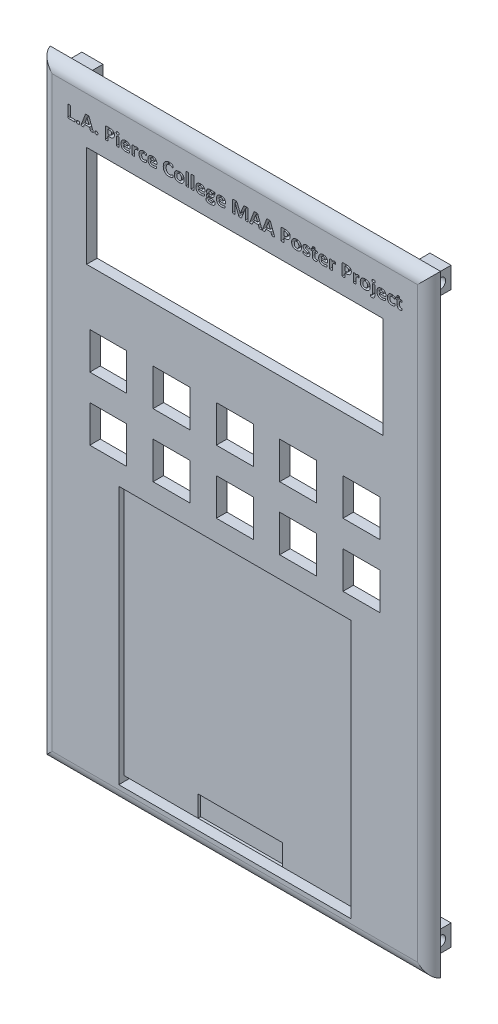
SolidWorks part; units mm, degrees
ref_plane "Front Plane" through (0, 0, 0) normal (0, 0, 1) x (1, 0, 0)
ref_plane "Top Plane" through (0, 0, 0) normal (0, 1, 0) x (1, 0, 0)
ref_plane "Right Plane" through (0, 0, 0) normal (1, 0, 0) x (0, 0, -1)
sketch "Sketch3" plane through (0, 0, 0) normal (0, 0, 1) x (1, 0, 0)
  line L1 (0, 184.15) -> (117.475, 184.15)
  line L2 (0, 184.15) -> (0, 0)
  line L3 (0, 0) -> (117.475, 0)
  line L4 (117.475, 184.15) -> (117.475, 0)
  dimension "D1" = 184.15
  dimension "D2" = 117.475
extrude "Boss-Extrude2" add sketch "Sketch3" along normal blind 3.175
sketch "Sketch6" plane through (0, 0, 3.175) normal (0, 0, 1) x (1, 0, 0)
  line L0 (0, 184.15) -> (0, 0) construction
  line L1 (34.1312, 119.38) -> (45.2437, 119.38)
  line L2 (34.1312, 119.38) -> (34.1312, 108.2675)
  line L3 (34.1312, 108.2675) -> (45.2437, 108.2675)
  line L4 (45.2437, 119.38) -> (45.2437, 108.2675)
  line L5 (53.1812, 119.38) -> (64.2937, 119.38)
  line L6 (53.1812, 119.38) -> (53.1812, 108.2675)
  line L7 (53.1812, 108.2675) -> (64.2937, 108.2675)
  line L8 (64.2937, 119.38) -> (64.2937, 108.2675)
  line L9 (72.2312, 119.38) -> (83.3437, 119.38)
  line L10 (72.2312, 119.38) -> (72.2312, 108.2675)
  line L11 (72.2312, 108.2675) -> (83.3437, 108.2675)
  line L12 (83.3437, 119.38) -> (83.3437, 108.2675)
  line L13 (91.2812, 119.38) -> (102.3937, 119.38)
  line L14 (91.2812, 119.38) -> (91.2812, 108.2675)
  line L15 (91.2812, 108.2675) -> (102.3937, 108.2675)
  line L16 (102.3937, 119.38) -> (102.3937, 108.2675)
  line L17 (15.0812, 119.38) -> (26.1937, 119.38)
  line L18 (15.0812, 119.38) -> (15.0812, 108.2675)
  line L19 (15.0812, 108.2675) -> (26.1937, 108.2675)
  line L20 (26.1937, 119.38) -> (26.1937, 108.2675)
  line L21 (15.0812, 100.33) -> (26.1937, 100.33)
  line L22 (15.0812, 100.33) -> (15.0812, 89.2175)
  line L23 (15.0812, 89.2175) -> (26.1937, 89.2175)
  line L24 (26.1937, 100.33) -> (26.1937, 89.2175)
  line L25 (34.1312, 100.33) -> (45.2437, 100.33)
  line L26 (34.1312, 100.33) -> (34.1312, 89.2175)
  line L27 (34.1312, 89.2175) -> (45.2437, 89.2175)
  line L28 (45.2437, 100.33) -> (45.2437, 89.2175)
  line L29 (53.1812, 100.33) -> (64.2937, 100.33)
  line L30 (53.1812, 100.33) -> (53.1812, 89.2175)
  line L31 (53.1812, 89.2175) -> (64.2937, 89.2175)
  line L32 (64.2937, 100.33) -> (64.2937, 89.2175)
  line L33 (72.2312, 100.33) -> (83.3437, 100.33)
  line L34 (72.2312, 100.33) -> (72.2312, 89.2175)
  line L35 (72.2312, 89.2175) -> (83.3437, 89.2175)
  line L36 (83.3437, 100.33) -> (83.3437, 89.2175)
  line L37 (91.2812, 100.33) -> (102.3937, 100.33)
  line L38 (91.2812, 100.33) -> (91.2812, 89.2175)
  line L39 (91.2812, 89.2175) -> (102.3937, 89.2175)
  line L40 (102.3937, 100.33) -> (102.3937, 89.2175)
  line L42 (117.475, 184.15) -> (0, 184.15) construction
  dimension "D1" = 11.1125
  dimension "D2" = 11.1125
  dimension "D3" = 11.1125
  dimension "D4" = 11.1125
  dimension "D5" = 11.1125
  dimension "D6" = 11.1125
  dimension "D7" = 11.1125
  dimension "D8" = 11.1125
  dimension "D9" = 11.1125
  dimension "D10" = 11.1125
  dimension "D11" = 7.9375
  dimension "D12" = 7.9375
  dimension "D13" = 7.9375
  dimension "D14" = 7.9375
  dimension "D15" = 15.0812
  dimension "D16" = 11.1125
  dimension "D17" = 11.1125
  dimension "D18" = 11.1125
  dimension "D19" = 11.1125
  dimension "D20" = 11.1125
  dimension "D21" = 11.1125
  dimension "D22" = 11.1125
  dimension "D23" = 11.1125
  dimension "D24" = 11.1125
  dimension "D25" = 11.1125
  dimension "D26" = 7.9375
  dimension "D27" = 7.9375
  dimension "D28" = 7.9375
  dimension "D29" = 7.9375
  dimension "D30" = 15.0812
  dimension "D31" = 7.9375
  dimension "D32" = 7.9375
  dimension "D33" = 7.9375
  dimension "D34" = 7.9375
  dimension "D35" = 7.9375
  dimension "D36" = 64.77
  dimension "D37" = 64.77
  dimension "D38" = 64.77
  dimension "D39" = 64.77
  dimension "D40" = 64.77
extrude "Cut-Extrude3" cut sketch "Sketch6" against normal through all
sketch "Sketch7" plane through (0, 0, 3.175) normal (0, 0, 1) x (1, 0, 0)
  line L0 (0, 184.15) -> (0, 0) construction
  line L1 (14.1287, 166.37) -> (103.3462, 166.37)
  line L2 (14.1287, 166.37) -> (14.1287, 135.89)
  line L3 (14.1287, 135.89) -> (103.3462, 135.89)
  line L4 (103.3462, 166.37) -> (103.3462, 135.89)
  line L5 (117.475, 184.15) -> (0, 184.15) construction
  point P6 (58.7375, 184.15)
  dimension "D1" = 14.1288
  dimension "D2" = 30.48
  dimension "D3" = 89.2175
  dimension "D4" = 17.78
extrude "Cut-Extrude4" cut sketch "Sketch7" against normal through all
sketch "Sketch8" plane through (0, 0, 3.175) normal (0, 0, 1) x (1, 0, 0)
  line L0 (0, 0) -> (117.475, 0) construction
  line L1 (23.8125, 82.8675) -> (93.6625, 82.8675)
  line L2 (23.8125, 82.8675) -> (23.8125, 5.08)
  line L3 (23.8125, 5.08) -> (93.6625, 5.08)
  line L4 (93.6625, 82.8675) -> (93.6625, 5.08)
  line L5 (0, 184.15) -> (0, 0) construction
  dimension "D1" = 77.7875
  dimension "D2" = 5.08
  dimension "D3" = 23.8125
  dimension "D4" = 69.85
extrude "Cut-Extrude5" cut sketch "Sketch8" against normal blind 1.5875
sketch "Sketch9" plane through (0, 0, 1.5875) normal (0, 0, 1) x (1, 0, 0)
  line L0 (23.8125, 82.8675) -> (23.8125, 5.08) construction
  line L1 (23.8125, 6.6675) -> (93.6625, 6.6675)
  line L2 (23.8125, 6.6675) -> (23.8125, 5.08)
  line L3 (23.8125, 5.08) -> (93.6625, 5.08)
  line L4 (93.6625, 6.6675) -> (93.6625, 5.08)
  line L5 (23.8125, 5.08) -> (93.6625, 5.08) construction
  line L6 (117.475, 0) -> (117.475, 184.15) construction
  dimension "D1" = 1.5875
  dimension "D2" = 23.8125
extrude "Cut-Extrude6" cut sketch "Sketch9" against normal through all
sketch "Sketch10" plane through (0, 0, 1.5875) normal (0, 0, 1) x (1, 0, 0)
  line L0 (93.6625, 6.6675) -> (23.8125, 6.6675) construction
  line L1 (46.0375, 13.0175) -> (71.4375, 13.0175)
  line L2 (46.0375, 13.0175) -> (46.0375, 6.6675)
  line L3 (46.0375, 6.6675) -> (71.4375, 6.6675)
  line L4 (71.4375, 13.0175) -> (71.4375, 6.6675)
  line L5 (0, 184.15) -> (0, 0) construction
  dimension "D1" = 25.4
  dimension "D2" = 46.0375
  dimension "D3" = 6.35
extrude "Cut-Extrude7" cut sketch "Sketch10" against normal blind 0.7937
fillet "Fillet1" radius 3.81 4 edges at (58.7375, 0, 3.175) (117.475, 92.075, 3.175) (0, 92.075, 3.175) (58.7375, 184.15, 3.175)
sketch "Sketch13" plane through (0, 0, 0) normal (0, 0, -1) x (-1, 0, 0)
  line L0 (-117.475, 0) -> (-117.475, 184.15) construction
  line L1 (-114.3, 180.975) -> (-3.175, 180.975)
  line L2 (-114.3, 180.975) -> (-114.3, 3.175)
  line L3 (-114.3, 3.175) -> (-3.175, 3.175)
  line L4 (-3.175, 180.975) -> (-3.175, 3.175)
  line L5 (0, 0) -> (-117.475, 0) construction
  line L7 (-112.7125, 179.3875) -> (-4.7625, 179.3875)
  line L8 (-112.7125, 179.3875) -> (-112.7125, 4.7625)
  line L9 (-112.7125, 4.7625) -> (-4.7625, 4.7625)
  line L10 (-4.7625, 179.3875) -> (-4.7625, 4.7625)
  dimension "D1" = 177.8
  dimension "D2" = 111.125
  dimension "D3" = 3.175
  dimension "D4" = 3.175
  dimension "D5" = 174.625
  dimension "D6" = 107.95
  dimension "D7" = 4.7625
  dimension "D8" = 4.7625
extrude "Boss-Extrude4" add sketch "Sketch13" along normal blind 3.175
sketch "Sketch14" plane through (0, 0, 0) normal (0, 0, -1) x (-1, 0, 0)
  line L1 (-114.3, 180.975) -> (-107.95, 180.975)
  line L2 (-114.3, 180.975) -> (-114.3, 174.625)
  line L3 (-114.3, 174.625) -> (-107.95, 174.625)
  line L4 (-107.95, 180.975) -> (-107.95, 174.625)
  line L5 (-3.175, 180.975) -> (-9.525, 180.975)
  line L6 (-3.175, 180.975) -> (-3.175, 174.625)
  line L7 (-3.175, 174.625) -> (-9.525, 174.625)
  line L8 (-9.525, 180.975) -> (-9.525, 174.625)
  line L9 (-114.3, 3.175) -> (-107.95, 3.175)
  line L10 (-114.3, 3.175) -> (-114.3, 9.525)
  line L11 (-114.3, 9.525) -> (-107.95, 9.525)
  line L12 (-107.95, 3.175) -> (-107.95, 9.525)
  line L13 (-3.175, 3.175) -> (-9.525, 3.175)
  line L14 (-3.175, 3.175) -> (-3.175, 9.525)
  line L15 (-3.175, 9.525) -> (-9.525, 9.525)
  line L16 (-9.525, 3.175) -> (-9.525, 9.525)
  dimension "D1" = 6.35
  dimension "D2" = 6.35
  dimension "D3" = 6.35
  dimension "D4" = 6.35
  dimension "D5" = 6.35
  dimension "D6" = 6.35
extrude "Boss-Extrude5" add sketch "Sketch14" along normal blind 6.35
fillet "Fillet9" radius 0.381 20 edges at (58.7375, 179.3875, 0) (4.7625, 92.075, 0) (58.7375, 4.7625, 0) (112.7125, 92.075, 0) (107.95, 179.3875, -1.5875) (107.95, 177.0062, 0) (110.3312, 174.625, 0) (112.7125, 174.625, -1.5875) (9.525, 179.3875, -1.5875) (9.525, 177.0062, 0) (7.1437, 174.625, 0) (4.7625, 174.625, -1.5875) (4.7625, 9.525, -1.5875) (7.1437, 9.525, 0) (9.525, 7.1437, 0) (9.525, 4.7625, -1.5875) (107.95, 4.7625, -1.5875) (107.95, 7.1437, 0) (110.3312, 9.525, 0) (112.7125, 9.525, -1.5875)
sketch "Sketch15" plane through (114.3, 0, 0) normal (1, 0, 0) x (0, 0, -1)
  line L0 (0, 180.975) -> (0, 3.175) construction
  line L1 (6.35, 3.175) -> (0, 3.175) construction
  line L2 (6.35, 9.525) -> (6.35, 3.175) construction
  line L4 (6.35, 180.975) -> (0, 180.975) construction
  circle A0 centre (3.175, 177.8) radius 1.524
  circle A1 centre (3.175, 6.35) radius 1.524
  circle A2 centre (3.175, 6.35) radius 1.524
  dimension "D2" = 3.048
  dimension "D6" = 3.048
  dimension "D1" = 3.175
  dimension "D3" = 3.175
  dimension "D4" = 3.175
  dimension "D5" = 3.175
extrude "Cut-Extrude9" cut sketch "Sketch15" against normal blind 6.35 contours A1 | A0 region at (114.3, 177.8, -3.175) region at (114.3, 6.35, -3.175)
sketch "Sketch16" plane through (3.175, 0, 0) normal (-1, 0, 0) x (0, 0, 1)
  line L0 (-6.35, 174.625) -> (-6.35, 180.975) construction
  line L1 (-6.35, 180.975) -> (0, 180.975) construction
  line L2 (-6.35, 3.175) -> (-6.35, 9.525) construction
  line L3 (-6.35, 3.175) -> (0, 3.175) construction
  circle A0 centre (-3.175, 177.8) radius 1.524
  circle A1 centre (-3.175, 6.35) radius 1.524
  dimension "D3" = 3.048
  dimension "D6" = 3.048
  dimension "D1" = 3.175
  dimension "D2" = 3.175
  dimension "D4" = 3.175
  dimension "D5" = 3.175
extrude "Cut-Extrude10" cut sketch "Sketch16" against normal blind 6.35
sketch "Sketch17" plane through (0, 0, 0) normal (0, 0, -1) x (-1, 0, 0)
  line L1 (-110.1725, 105.5291) -> (-106.9975, 105.5291)
  line L2 (-110.1725, 105.5291) -> (-110.1725, 100.7666)
  line L3 (-110.1725, 100.7666) -> (-106.9975, 100.7666)
  line L4 (-106.9975, 105.5291) -> (-106.9975, 100.7666)
  line L5 (-10.4775, 105.5291) -> (-7.3025, 105.5291)
  line L6 (-10.4775, 105.5291) -> (-10.4775, 100.7666)
  line L7 (-10.4775, 100.7666) -> (-7.3025, 100.7666)
  line L8 (-7.3025, 105.5291) -> (-7.3025, 100.7666)
  line L10 (-112.7125, 174.244) -> (-112.7125, 9.906) construction
  line L11 (-4.7625, 9.906) -> (-4.7625, 174.244) construction
  dimension "D1" = 4.7625
  dimension "D2" = 4.7625
  dimension "D3" = 3.175
  dimension "D4" = 2.54
  dimension "D5" = 2.54
  dimension "D6" = 3.175
extrude "Boss-Extrude6" add sketch "Sketch17" along normal blind 4.7625
sketch "Sketch18" plane through (0, 105.5291, 0) normal (0, 1, 0) x (1, 0, 0)
  line L1 (110.1725, 0) -> (108.585, 0)
  line L2 (110.1725, 0) -> (110.1725, 3.175)
  line L3 (110.1725, 3.175) -> (108.585, 3.175)
  line L4 (108.585, 0) -> (108.585, 3.175)
  dimension "D1" = 3.175
  dimension "D2" = 1.5875
extrude "Cut-Extrude11" cut sketch "Sketch18" against normal blind 4.7625
sketch "Sketch19" plane through (0, 105.5291, 0) normal (0, 1, 0) x (1, 0, 0)
  line L1 (7.3025, 0) -> (8.89, 0)
  line L2 (7.3025, 0) -> (7.3025, 3.175)
  line L3 (7.3025, 3.175) -> (8.89, 3.175)
  line L4 (8.89, 0) -> (8.89, 3.175)
  dimension "D1" = 3.175
  dimension "D2" = 1.5875
extrude "Cut-Extrude12" cut sketch "Sketch19" against normal blind 4.7625
fillet "Fillet10" radius 1.905 8 edges at (107.7912, 105.5291, 0) (108.585, 103.1478, 0) (107.7912, 100.7666, 0) (106.9975, 103.1478, 0) (8.89, 103.1478, 0) (9.6837, 100.7666, 0) (10.4775, 103.1478, 0) (9.6837, 105.5291, 0)
fillet "Fillet13" radius 0.381 6 edges at (108.585, 103.1478, -3.175) (8.89, 103.1478, -3.175) (106.9975, 103.1478, -4.7625) (110.1725, 103.1478, -4.7625) (10.4775, 103.1478, -4.7625) (7.3025, 103.1478, -4.7625)
sketch "Sketch20" plane through (0, 0, 3.175) normal (0, 0, 1) x (1, 0, 0)
  text T0 "L.A. Pierce College MAA Poster Project" font "Calibri" height in points 14
extrude "Cut-Extrude13" cut sketch "Sketch20" against normal blind 1.5875
